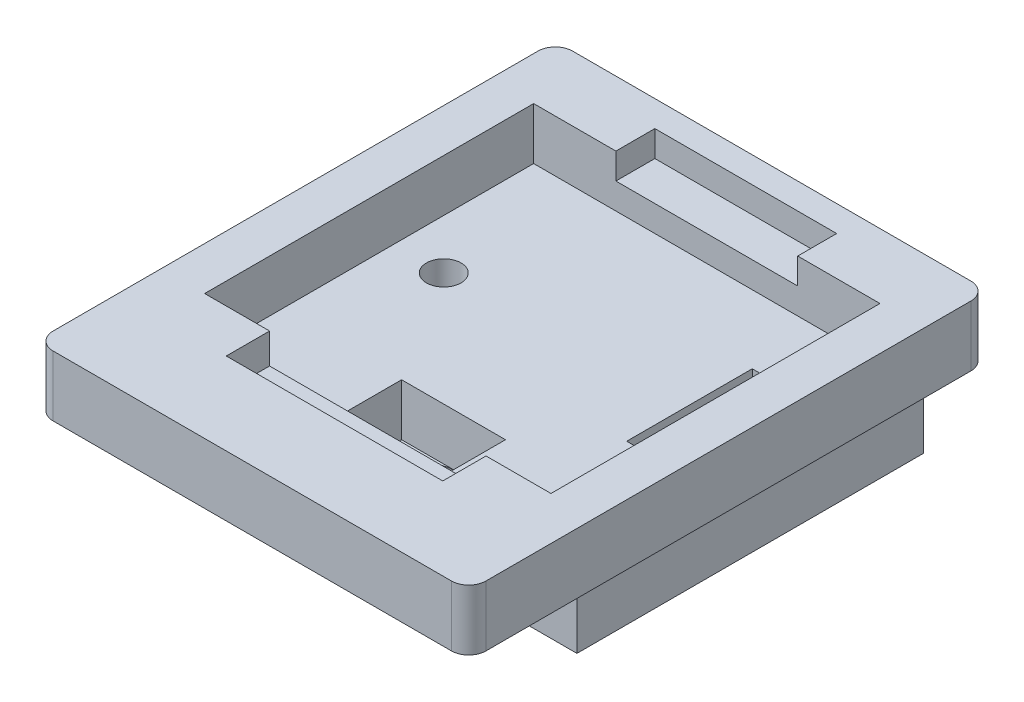
SolidWorks part; units mm, degrees
ref_plane "Front Plane" through (0, 0, 0) normal (0, 0, 1) x (1, 0, 0)
ref_plane "Top Plane" through (0, 0, 0) normal (0, 1, 0) x (1, 0, 0)
ref_plane "Right Plane" through (0, 0, 0) normal (1, 0, 0) x (0, 0, -1)
sketch "Sketch1" plane through (0, 0, 0) normal (0, 1, 0) x (1, 0, 0)
  line L1 (-25, 30) -> (25, 30)
  line L2 (-25, 30) -> (-25, -30)
  line L3 (-25, -30) -> (25, -30)
  line L4 (25, 30) -> (25, -30)
  line L5 (-25, 30) -> (25, -30) construction
  line L6 (-25, -30) -> (25, 30) construction
  point P0 (0, 0)
  dimension "D1" = 60
  dimension "D2" = 50
extrude "Boss-Extrude1" add sketch "Sketch1" along normal blind 15
fillet "Fillet1" radius 2 4 edges at (-25, 7.5, 30) (25, 7.5, 30) (25, 7.5, -30) (-25, 7.5, -30)
sketch "Sketch2" plane through (0, 15, 0) normal (0, 1, 0) x (1, 0, 0)
  line L0 (-20, -15.5) -> (20, -15.5)
  line L1 (-20, 22.5) -> (20, 22.5)
  line L3 (20, -15.5) -> (20, 22.5)
  line L5 (-20, 22.5) -> (20, -22.5) construction
  line L6 (-20, -22.5) -> (20, 22.5) construction
  line L7 (-20, 22.5) -> (-20, -15.5)
  point P0 (0, 0)
  dimension "D1" = 38
  dimension "D2" = 40
extrude "Cut-Extrude1" cut sketch "Sketch2" against normal blind 6
sketch "Sketch3" plane through (0, 9, 0) normal (0, 1, 0) x (1, 0, 0)
  line L0 (16.4, 13.7) -> (13.9, 1) construction
  line L1 (13.9, 1) -> (16.4, 1) construction
  line L2 (16.4, 1) -> (13.9, 13.7) construction
  line L3 (13.9, 13.7) -> (15.15, 7.35) construction
  line L5 (13.15, 14.6) -> (17.15, 14.6)
  line L6 (13.15, 14.6) -> (13.15, 0.1)
  line L7 (13.15, 0.1) -> (17.15, 0.1)
  line L8 (17.15, 14.6) -> (17.15, 0.1)
  line L9 (13.15, 14.6) -> (17.15, 0.1) construction
  line L10 (13.15, 0.1) -> (17.15, 14.6) construction
  dimension "D1" = 14.5
  dimension "D2" = 4
extrude "Cut-Extrude2" cut sketch "Sketch3" against normal blind 10
sketch "Sketch4" plane through (0, 0, 0) normal (0, -1, 0) x (1, 0, 0)
  circle A0 centre (-14.252, -6.369) radius 2
  dimension "D1" = 4
extrude "Cut-Extrude3" cut sketch "Sketch4" against normal blind 10
sketch "Sketch5" plane through (0, 9, 0) normal (0, 1, 0) x (1, 0, 0)
  line L0 (-5.75, -7) -> (5.75, -13) construction
  line L1 (-5.75, -13) -> (5.75, -13) construction
  line L2 (5.75, -13) -> (5.75, -7) construction
  line L3 (5.75, -7) -> (5.75, -13) construction
  line L4 (-5.75, -7) -> (5.75, -7) construction
  line L5 (5.75, -7) -> (-5.75, -13) construction
  line L6 (-5.75, -13) -> (0, -10) construction
  line L8 (-6, -6.75) -> (6, -6.75)
  line L9 (-6, -6.75) -> (-6, -13.25)
  line L10 (-6, -13.25) -> (6, -13.25)
  line L11 (6, -6.75) -> (6, -13.25)
  line L12 (-6, -6.75) -> (6, -13.25) construction
  line L13 (-6, -13.25) -> (6, -6.75) construction
  dimension "D1" = 6.5
  dimension "D2" = 12
extrude "Cut-Extrude4" cut sketch "Sketch5" against normal blind 6
sketch "Sketch6" plane through (0, 0, 0) normal (0, -1, 0) x (1, 0, 0)
  circle A0 centre (0, 10) radius 3.2
  dimension "D1" = 6.4
extrude "Cut-Extrude5" cut sketch "Sketch6" against normal blind 8
sketch "Sketch7" plane through (0, 15, 0) normal (0, 1, 0) x (1, 0, 0)
  line L0 (-20, -15.5) -> (20, -15.5) construction
  line L1 (-12.5, -10.5) -> (12.5, -10.5)
  line L2 (-12.5, -10.5) -> (-12.5, -20.5)
  line L3 (-12.5, -20.5) -> (12.5, -20.5)
  line L4 (12.5, -10.5) -> (12.5, -20.5)
  line L5 (-12.5, -10.5) -> (12.5, -20.5) construction
  line L6 (-12.5, -20.5) -> (12.5, -10.5) construction
  point P0 (0, -15.5)
  dimension "D1" = 10
  dimension "D2" = 25
extrude "Cut-Extrude6" cut sketch "Sketch7" against normal blind 3.5
sketch "Sketch8" plane through (0, 0, 0) normal (0, -1, 0) x (-1, 0, 0)
  line L1 (0, 30) -> (0, 5) construction
  line L2 (-23, 30) -> (23, 30) construction
  line L5 (-22.5, 25) -> (22.5, 25)
  line L6 (-22.5, 25) -> (-22.5, -15)
  line L7 (-22.5, -15) -> (22.5, -15)
  line L8 (22.5, 25) -> (22.5, -15)
  line L9 (-22.5, 25) -> (22.5, -15) construction
  line L10 (-22.5, -15) -> (22.5, 25) construction
  line L11 (-25.6961, 31.0422) -> (25.6961, 31.0422)
  line L12 (-25.6961, 31.0422) -> (-25.6961, -31.0422)
  line L13 (-25.6961, -31.0422) -> (25.6961, -31.0422)
  line L14 (25.6961, 31.0422) -> (25.6961, -31.0422)
  line L15 (-25.6961, 31.0422) -> (25.6961, -31.0422) construction
  line L16 (-25.6961, -31.0422) -> (25.6961, 31.0422) construction
  point P10 (0, 0)
  dimension "D1" = 25
  dimension "D2" = 40
  dimension "D3" = 45
extrude "Cut-Extrude7" cut sketch "Sketch8" against normal blind 8
sketch "Sketch9" plane through (0, 15, 0) normal (0, 1, 0) x (1, 0, 0)
  line L1 (-10.5, 18) -> (10.5, 18)
  line L2 (-10.5, 18) -> (-10.5, 27)
  line L3 (-10.5, 27) -> (10.5, 27)
  line L4 (10.5, 18) -> (10.5, 27)
extrude "Cut-Extrude8" cut sketch "Sketch9" against normal blind 3
fillet "Fillet2" radius 2 4 edges at (-22.5, 8, -5) (0, 8, -25) (22.5, 8, -5) (0, 8, 15)
